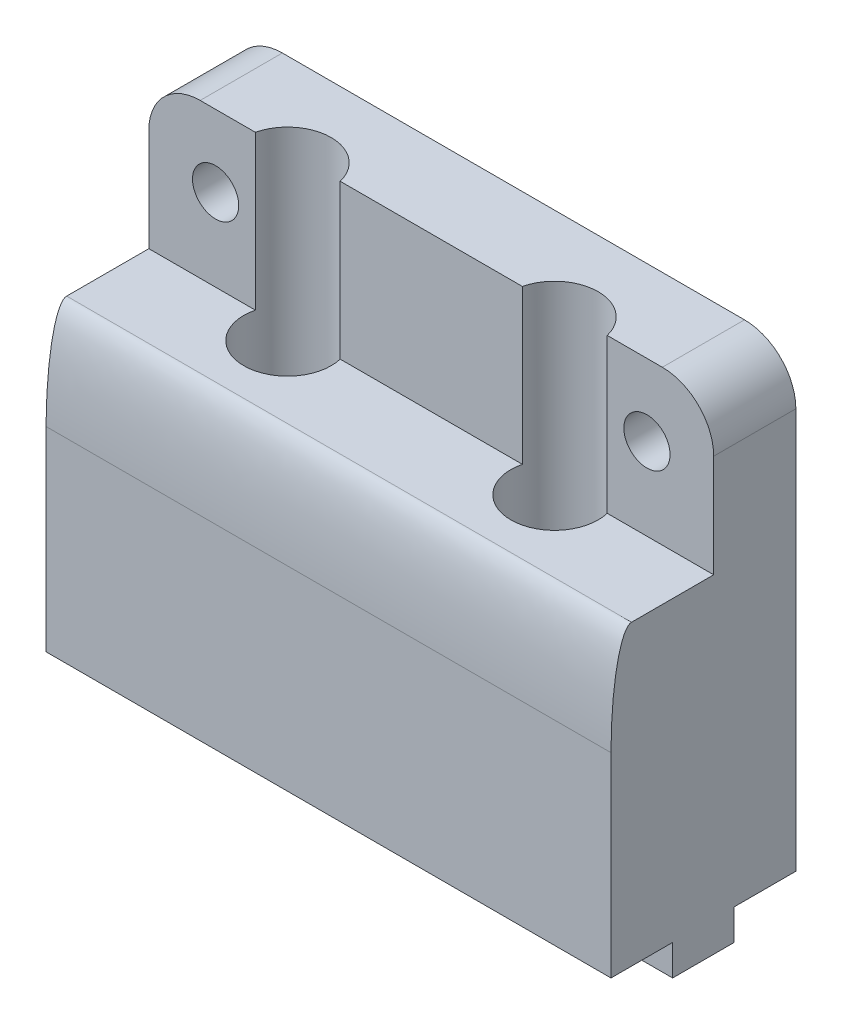
SolidWorks part; units mm, degrees
ref_plane "Спереди" through (0, 0, 0) normal (0, 0, 1) x (1, 0, 0)
ref_plane "Сверху" through (0, 0, 0) normal (0, 1, 0) x (1, 0, 0)
ref_plane "Справа" through (0, 0, 0) normal (1, 0, 0) x (0, 0, -1)
sketch "Эскиз1" plane through (0, 0, 0) normal (0, 1, 0) x (1, 0, 0)
  line L1 (0, 0) -> (55, 0)
  line L2 (0, 0) -> (0, 18)
  line L3 (0, 18) -> (55, 18)
  line L4 (55, 0) -> (55, 18)
  dimension "D1" = 18
  dimension "D2" = 55
extrude "Бобышка-Вытянуть1" add sketch "Эскиз1" along normal blind 44
sketch "Эскиз2" plane through (0, 0, 0) normal (0, 0, 1) x (1, 0, 0)
  line L0 (27.5, 58.1889) -> (27.5, -27.8347) construction
  line L1 (0, 44) -> (55, 44) construction
  line L2 (0, 44) -> (0, 0) construction
  circle A0 centre (48.5, 37) radius 2.25
  circle A1 centre (6.5, 37) radius 2.25
  point P8 (27.5, 44)
  dimension "D1" = 4.5
  dimension "D2" = 6.5
  dimension "D3" = 7
extrude "Вырез-Вытянуть1" cut sketch "Эскиз2" against normal blind 40
sketch "Эскиз3" plane through (0, 44, 0) normal (0, 1, 0) x (1, 0, 0)
  line L0 (27.5, 18) -> (27.5, 0) construction
  line L1 (55, 18) -> (0, 18) construction
  line L2 (0, 0) -> (55, 0) construction
  circle A0 centre (40.5, 9) radius 2.25
  circle A1 centre (14.5, 9) radius 2.25
  point P9 (27.5, 9)
  dimension "D1" = 4.5
  dimension "D2" = 13
extrude "Вырез-Вытянуть2" cut sketch "Эскиз3" against normal blind 50
sketch "Эскиз4" plane through (0, 44, 0) normal (0, 1, 0) x (1, 0, 0)
  circle A0 centre (40.5, 9) radius 4.25
  circle A1 centre (14.5, 9) radius 4.25
  dimension "D1" = 8.5
  dimension "D2" = 8.5
extrude "Вырез-Вытянуть3" cut sketch "Эскиз4" against normal blind 22
sketch "Эскиз5" plane through (0, 0, -18) normal (0, 0, -1) x (-1, 0, 0)
  line L1 (-46.3638, 33.3) -> (-44.2276, 37)
  line L2 (-44.2276, 37) -> (-46.3638, 40.7)
  line L3 (-46.3638, 40.7) -> (-50.6362, 40.7)
  line L4 (-50.6362, 40.7) -> (-52.7724, 37)
  line L5 (-52.7724, 37) -> (-50.6362, 33.3)
  line L6 (-50.6362, 33.3) -> (-46.3638, 33.3)
  line L7 (-4.3638, 33.3) -> (-2.2276, 37)
  line L8 (-2.2276, 37) -> (-4.3638, 40.7)
  line L9 (-4.3638, 40.7) -> (-8.6362, 40.7)
  line L10 (-8.6362, 40.7) -> (-10.7724, 37)
  line L11 (-10.7724, 37) -> (-8.6362, 33.3)
  line L12 (-8.6362, 33.3) -> (-4.3638, 33.3)
  circle A0 centre (-48.5, 37) radius 3.7 construction
  circle A1 centre (-6.5, 37) radius 3.7 construction
  circle M1 centre (-6.5, 37) radius 2.25
  circle M2 centre (-48.5, 37) radius 2.25
  dimension "D1" = 7.4
extrude "Вырез-Вытянуть4" cut sketch "Эскиз5" against normal blind 4 contours L5 L6 L1 L2 L3 L4 M2 | L11 L12 L7 L8 L9 L10 M1 region at (48.5, 33.413, -18) region at (6.5, 33.413, -18)
fillet "Скругление1" radius 5 2 edges at (0, 44, -9) (55, 44, -9)
sketch "Эскиз6" plane through (0, 0, 0) normal (0, -1, 0) x (1, 0, 0)
  line L0 (55, 0) -> (55, -18) construction
  line L1 (55, -6) -> (47, -6)
  line L2 (55, -6) -> (55, -12)
  line L3 (55, -12) -> (47, -12)
  line L4 (47, -6) -> (47, -12)
  line L5 (0, -18) -> (0, 0) construction
  line L6 (0, -6) -> (8, -6)
  line L7 (0, -6) -> (0, -12)
  line L8 (0, -12) -> (8, -12)
  line L9 (8, -6) -> (8, -12)
  circle A0 centre (14.5, -9) radius 2.25 construction
  circle A1 centre (40.5, -9) radius 2.25 construction
  point P12 (0, -9)
  point P13 (0, -9)
  dimension "D2" = 6.5
  dimension "D3" = 6.5
  dimension "D1" = 6
extrude "Бобышка-Вытянуть2" add sketch "Эскиз6" along normal blind 3
sketch "Эскиз7" plane through (0, 0, 0) normal (0, 0, 1) x (1, 0, 0)
  line L0 (0, 39) -> (0, 0) construction
  line L1 (0, 29) -> (71.4359, 29)
  line L2 (0, 29) -> (0, 57.7864)
  line L3 (0, 57.7864) -> (71.4359, 57.7864)
  line L4 (71.4359, 29) -> (71.4359, 57.7864)
  line L5 (5, 44) -> (50, 44) construction
  dimension "D1" = 15
extrude "Вырез-Вытянуть5" cut sketch "Эскиз7" against normal blind 10
fillet "Скругление2" radius 10 1 edges at (27.5, 29, 0) second distance 2 first distance on face at (27.5, 14.5, 0)
